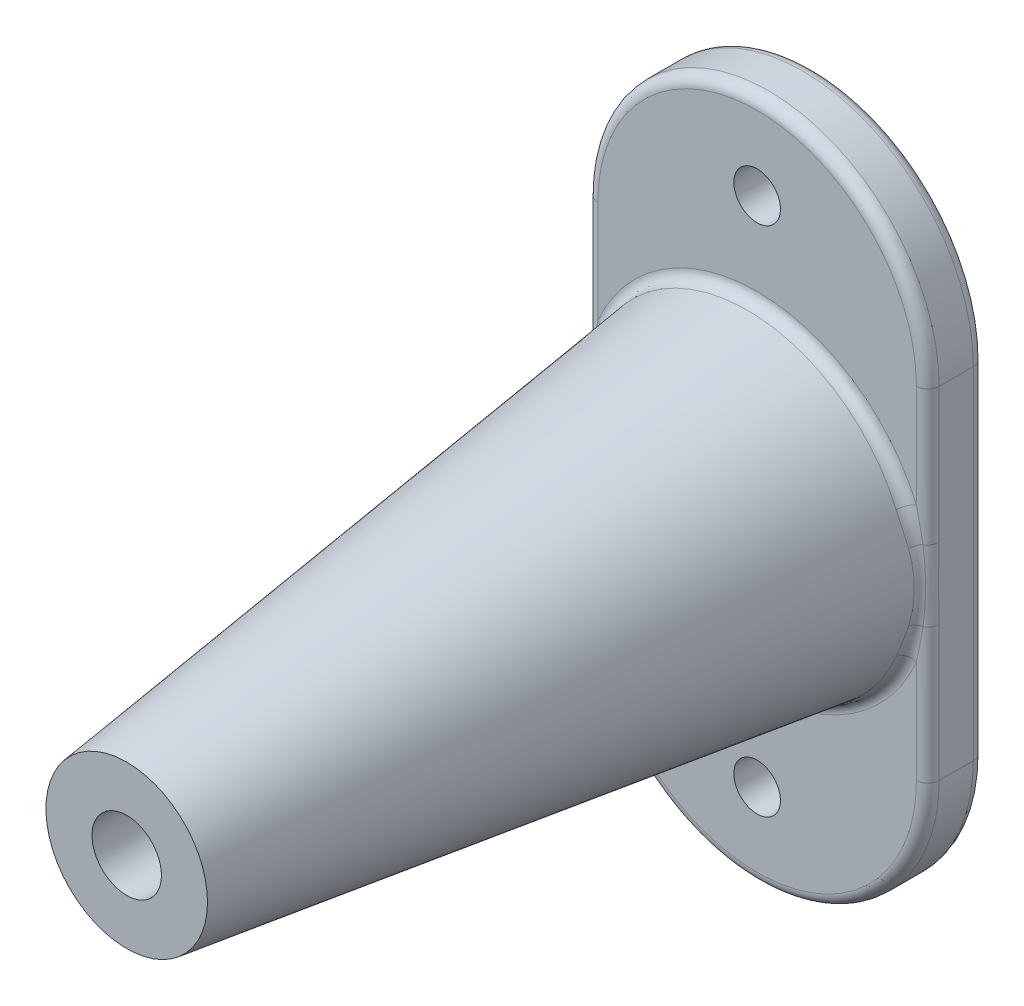
SolidWorks part; units mm, degrees
ref_plane "Plan de face" through (0, 0, 0) normal (0, 0, 1) x (1, 0, 0)
ref_plane "Plan de dessus" through (0, 0, 0) normal (0, 1, 0) x (1, 0, 0)
ref_plane "Plan de droite" through (0, 0, 0) normal (1, 0, 0) x (0, 0, -1)
sketch "Esquisse1" plane through (0, 0, 0) normal (0, 0, 1) x (1, 0, 0)
  circle A0 centre (0, 0) radius 15
  point P0 (0, 0)
  dimension "D1" = 30
ref_plane "Plan1" through (0, 0, 60.4) normal (0, 0, 1) x (1, 0, 0)
sketch "Esquisse2" plane through (0, 0, 60.4) normal (0, 0, 1) x (1, 0, 0)
  circle A0 centre (0, 0) radius 7.1
  dimension "D1" = 14.2
loft "Lissage1" add profiles "Esquisse1", "Esquisse2" connector at (-1.7116, 14.902, 0) connector at (-1.8526, 6.854, 60.4)
sketch "Esquisse3" plane through (0, 0, 0) normal (0, 0, -1) x (-1, 0, 0)
  line L0 (0, 0) -> (0, 30) construction
  line L1 (-15, 30) -> (15, 30)
  line L2 (-15, 30) -> (-15, -30)
  line L3 (-15, -30) -> (15, -30)
  line L4 (15, 30) -> (15, -30)
  line L5 (-15, 30) -> (15, -30) construction
  line L6 (-15, -30) -> (15, 30) construction
  line L7 (0, 0) -> (7.5515, 0) construction
  line L8 (0, 0) -> (0, -15) construction
  circle A0 centre (0, 22.5) radius 2.05
  circle A2 centre (0, -22.5) radius 2.05
  arc A3 (-15, -15) -> (15, -15) centre (0, -15) ccw
  arc A4 (-15, 15) -> (15, 15) centre (0, 15) cw
  point P0 (0, 0)
  dimension "D3" = 4.1
  dimension "D6" = 15
  dimension "D1" = 30
  dimension "D2" = 60
  dimension "D4" = 7.5
  dimension "D5" = 15
extrude "Boss.-Extru.1" add sketch "Esquisse3" against normal blind 5 contours L2 A3 L4 A2 | A4 L2 L4 A0 region at (0, 0, 0)
sketch "Esquisse4" plane through (0, 0, 60.4) normal (0, 0, 1) x (1, 0, 0)
  circle A0 centre (0, 0) radius 3.05
  dimension "D1" = 6.1
extrude "Enlèv. mat.-Extru.1" cut sketch "Esquisse4" against normal through all both and the other way through all
fillet "Congé3" radius 1 9 edges at (0, 30, 0) (0, 30, 5) (-15, 0, 5) (0, -30, 5) (0, -30, 0) (15, 0, 5)
fillet "Congé4" radius 1 4 edges at (-14.346, 0, 5) (0, 14.346, 5) (14.346, 0, 5) (0, -14.346, 5)
